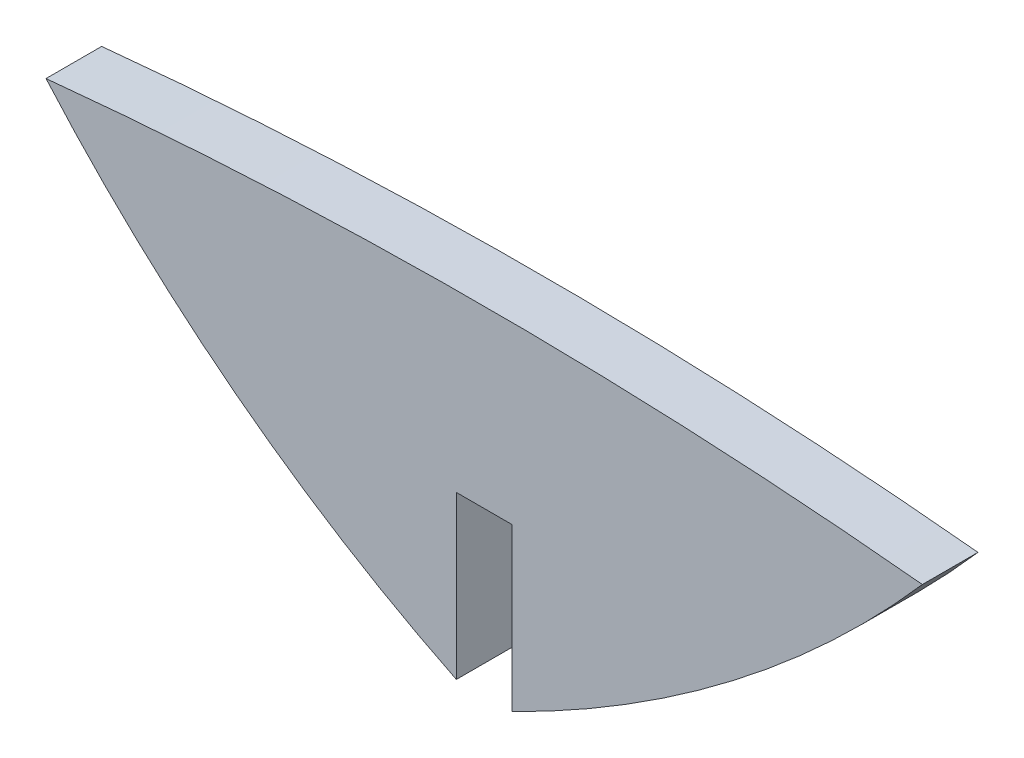
SolidWorks part; units mm, degrees
ref_plane "Front Plane" through (0, 0, 0) normal (0, 0, 1) x (1, 0, 0)
ref_plane "Top Plane" through (0, 0, 0) normal (0, 1, 0) x (1, 0, 0)
ref_plane "Right Plane" through (0, 0, 0) normal (1, 0, 0) x (0, 0, -1)
ref_plane "Plane1" through (0, 0, 1.5875) normal (0, 0, 1) x (1, 0, 0)
sketch "Sketch2" plane through (0, 0, 1.5875) normal (0, 0, 1) x (1, 0, 0)
  line L0 (-1.5875, 357.6599) -> (1.5875, 357.6599) construction
  line L1 (0, 325.0814) -> (0, 347.665) construction
  line L2 (-1.5875, 325.0814) -> (-1.5875, 347.665)
  line L3 (1.5875, 325.0814) -> (1.5875, 347.665)
  line L4 (-25, 356.4084) -> (25, 356.4084) construction
  line L5 (-1.5875, 347.665) -> (1.5875, 347.665)
  arc A2 (-25, 356.4084) -> (0, 337.665) centre (31.503, 405.7279) ccw
  arc A3 (0, 337.665) -> (25, 356.4084) centre (-31.503, 405.7279) ccw
  arc A4 (-1.5875, 325.0814) -> (1.5875, 325.0814) centre (0, 325.0814) ccw
  arc A5 (1.5875, 347.665) -> (-1.5875, 347.665) centre (0, 347.665) ccw
  arc A6 (25, 356.4084) -> (-25, 356.4084) centre (0, 107.34) ccw
  arc A7 (79.7117, 348.5081) -> (-79.7117, 348.5081) centre (0, 107.34) ccw construction
  point P10 (0, 357.6599)
  point P11 (0, 336.3732)
  point P14 (0, 356.4084)
  dimension "D2" = 75
  dimension "D1" = 10
  dimension "D3" = 50
extrude "Boss-Extrude1" add sketch "Sketch2" along normal mid plane 3.175 contours A5 L3 A3 A2 L2 | L5 A5 region at (0, 350.6408, 1.5875) region at (0, 348.3387, 1.5875)
